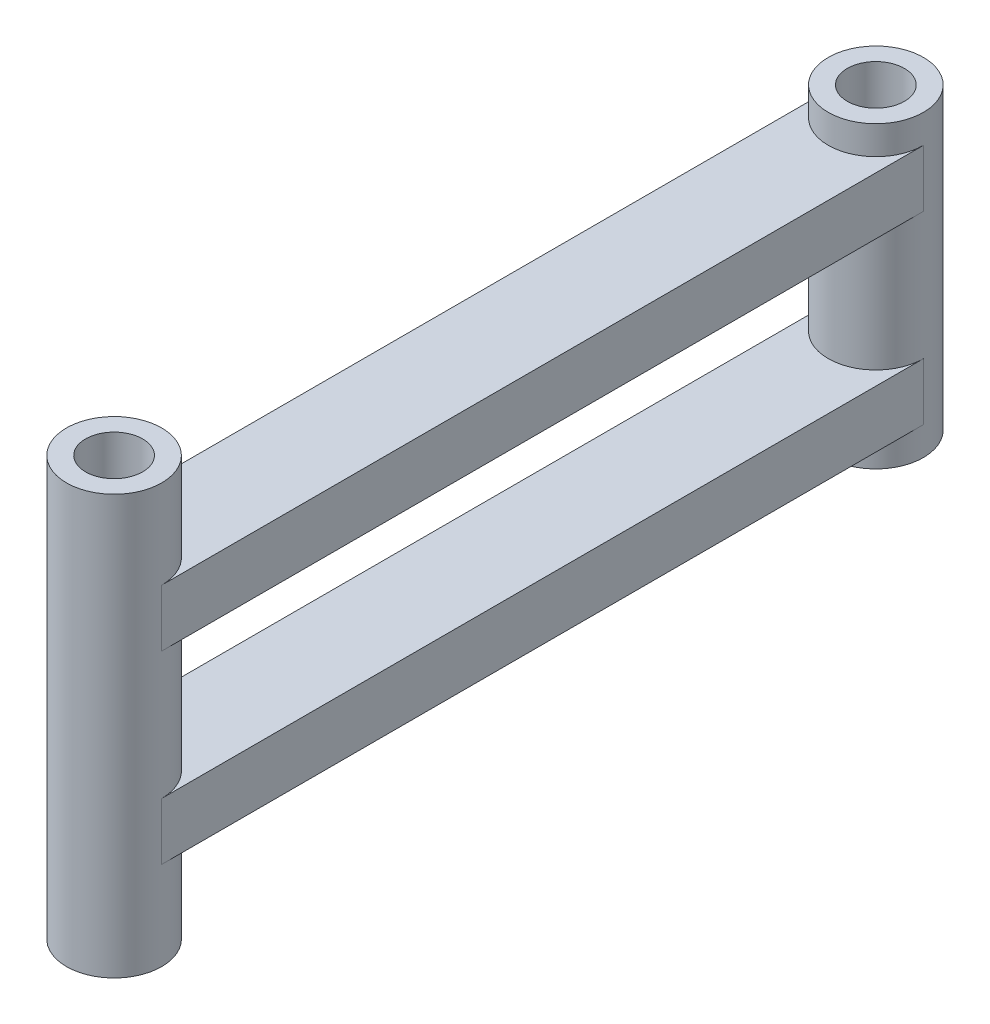
SolidWorks part; units mm, degrees
material "ABS"
ref_plane "Front Plane" through (0, 0, 0) normal (0, 0, 1) x (1, 0, 0)
ref_plane "Top Plane" through (0, 0, 0) normal (0, 1, 0) x (1, 0, 0)
ref_plane "Right Plane" through (0, 0, 0) normal (1, 0, 0) x (0, 0, -1)
sketch "Sketch1" plane through (0, 0, 0) normal (0, 1, 0) x (1, 0, 0)
  line L0 (0, 0) -> (0, -40) construction
  line L1 (2.5, 0) -> (2.5, -40)
  line L2 (-2.5, 0) -> (-2.5, -40)
  arc A0 (2.5, 0) -> (-2.5, 0) centre (0, 0) ccw
  arc A1 (-2.5, -40) -> (2.5, -40) centre (0, -40) ccw
  point P3 (0, -20)
  dimension "D2" = 2.5
  dimension "D1" = 40
extrude "Boss-Extrude1" add sketch "Sketch1" along normal blind 3 contours L1 A1 L2 A0
sketch "Sketch2" plane through (0, 3, 0) normal (0, 1, 0) x (1, 0, 0)
  circle A0 centre (0, 0) radius 2.5
  dimension "D1" = 5
extrude "Boss-Extrude2" add sketch "Sketch2" along normal blind 7.85 and the other way blind 7.85 from offset 3.35
extrude "Boss-Extrude3" add sketch "Sketch1<3>" against normal blind 3 from offset 12.7
sketch "Sketch1<3>" plane through (0, 0, 0) normal (0, 1, 0) x (1, 0, 0) same geometry as "Sketch1"
sketch "Sketch7" plane through (0, 3, 0) normal (0, 1, 0) x (1, 0, 0)
  circle A0 centre (0, -40) radius 2.5
  arc A1 (-2.5, -40) -> (2.5, -40) centre (0, -40) ccw construction
  point P3 (0, 0)
  point P7 (0, 0)
  dimension "D1" = 5
extrude "Boss-Extrude4" add sketch "Sketch7" along normal blind 11 and the other way blind 11 from offset 3.35
hole_wizard "Ø3.0mm Clearance Dowel Hole3" positions "Sketch8" profile "Sketch9" hole size "Ø3.0" standard "ANSI Metric" end condition through all
sketch "Sketch8" plane through (0, 17.35, 0) normal (0, 1, 0) x (1, 0, 0)
  point P0 (0, -40)
  point P3 (0, 0)
sketch "Sketch9" plane through (0, 17.35, 40) normal (1, 0, 0) x (0, 0, 1)
  line L0 (0, 0) -> (0, 22)
  line L1 (0, 22) -> (1.5, 22)
  line L2 (1.5, 22) -> (1.5, 0)
  line L5 (1.5, 0) -> (0, 0)
  line L11 (0, -6.35) -> (0, 107.95) construction
  dimension "Thru Hole Dia." = 3
  dimension "Thru Hole Depth" = 22
